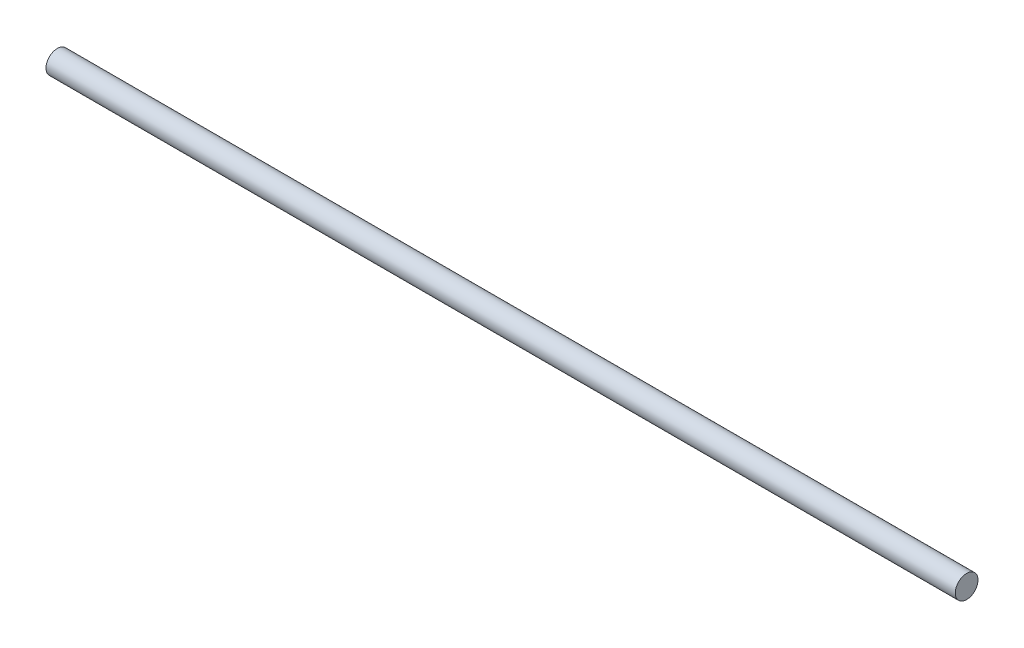
SolidWorks part; units mm, degrees
ref_plane "前视基准面" through (0, 0, 0) normal (0, 0, 1) x (1, 0, 0)
ref_plane "上视基准面" through (0, 0, 0) normal (0, 1, 0) x (1, 0, 0)
ref_plane "右视基准面" through (0, 0, 0) normal (1, 0, 0) x (0, 0, -1)
sketch "草图1" plane through (0, 0, 0) normal (1, 0, 0) x (0, 0, -1)
  circle A0 centre (0, 0) radius 1.25
  dimension "D1" = 2.5
extrude "凸台-拉伸1" add sketch "草图1" along normal blind 50 and the other way blind 50
